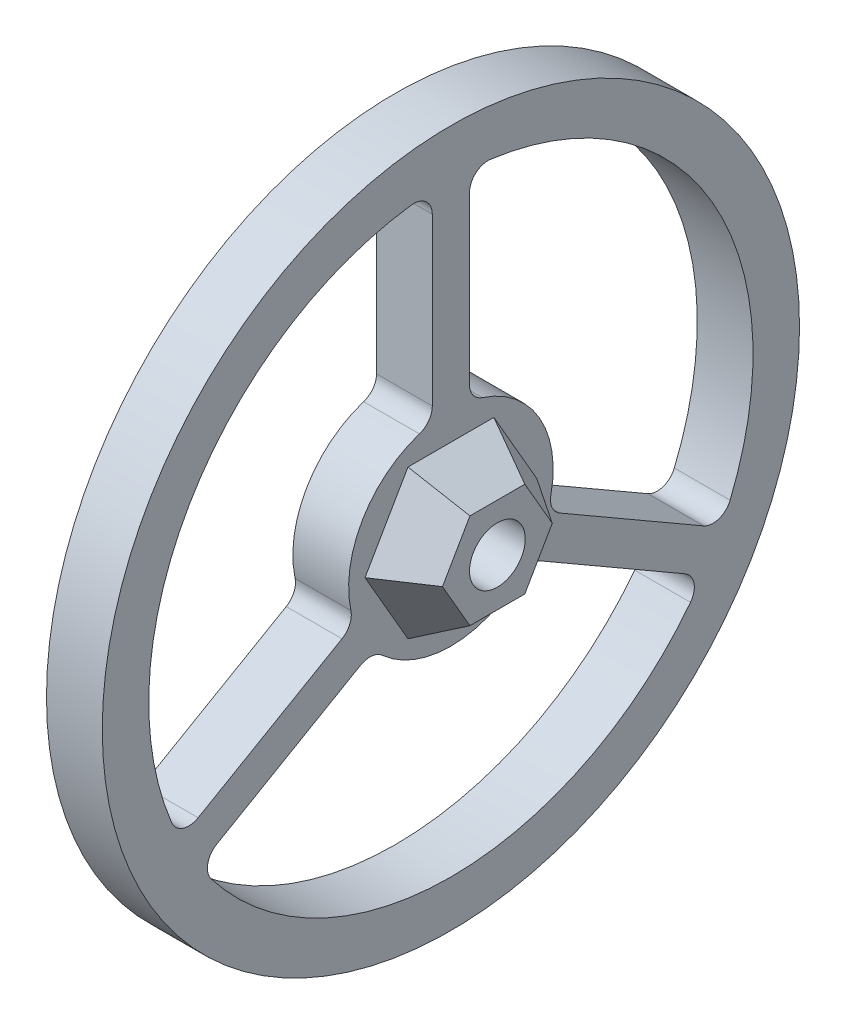
SolidWorks part; units mm, degrees
material "Acrylic (Medium-high impact)"
ref_plane "Front Plane" through (0, 0, 0) normal (0, 0, 1) x (1, 0, 0)
ref_plane "Top Plane" through (0, 0, 0) normal (0, 1, 0) x (1, 0, 0)
ref_plane "Right Plane" through (0, 0, 0) normal (1, 0, 0) x (0, 0, -1)
sketch "Sketch1" plane through (0, 0, 0) normal (1, 0, 0) x (0, 0, -1)
  line L0 (0, 0) -> (0, 37.5) construction
  line L1 (-2, 32.4384) -> (-2, 10.8167)
  line L2 (2, 32.4384) -> (2, 10.8167)
  line L3 (29.0925, -14.4872) -> (10.3675, -3.6763)
  line L4 (27.0925, -17.9513) -> (8.3675, -7.1404)
  line L5 (-27.0925, -17.9513) -> (-8.3675, -7.1404)
  line L6 (-29.0925, -14.4872) -> (-10.3675, -3.6763)
  circle A0 centre (0, 0) radius 37.5
  circle A2 centre (0, 0) radius 32.5
  circle A3 centre (0, 0) radius 3
  circle A4 centre (0, 0) radius 11
  point P23 (0, 0)
  dimension "D1" = 75
  dimension "D3" = 6
  dimension "D6" = 4
  dimension "D2" = 5
  dimension "D4" = 8
  dimension "D5" = 3
extrude "Boss-Extrude1" add sketch "Sketch1" along normal blind 6 contours A2 A0 | A3 A4 | A4 L6 A2 L5 | L0 A4 L2 A2 | A4 L0 A2 L1 | A4 L4 A2 L3 region at (0, 10.6442, -0.9758) region at (0, 21.7092, 1.0009) region at (0, 21.7092, -1.0009) region at (0, 25.7665, -25.7665) region at (0, -10.8546, 18.8007) region at (0, -10.8546, -18.8007)
fillet "Fillet1" radius 2 12 edges at (3, -3.6763, 10.3675) (3, -7.1404, 8.3675) (3, -7.1404, -8.3675) (3, -3.6763, -10.3675) (3, 10.8167, -2) (3, -17.9513, -27.0925) (3, -14.4872, -29.0925) (3, -17.9513, 27.0925) (3, -14.4872, 29.0925) (3, 32.4384, -2) (3, 32.4384, 2) (3, 10.8167, 2)
sketch "Sketch2" plane through (6, 0, 0) normal (1, 0, 0) x (0, 0, -1)
  line L1 (9.2376, 0) -> (4.6188, 8)
  line L2 (4.6188, 8) -> (-4.6188, 8)
  line L3 (-4.6188, 8) -> (-9.2376, 0)
  line L4 (-9.2376, 0) -> (-4.6188, -8)
  line L5 (-4.6188, -8) -> (4.6188, -8)
  line L6 (4.6188, -8) -> (9.2376, 0)
  circle A0 centre (0, 0) radius 8 construction
  dimension "D1" = 16
extrude "Boss-Extrude2" add sketch "Sketch2" along normal blind 5 draft 30
extrude "Cut-Extrude1" cut sketch "Sketch1<6>" along normal blind 20 contours A3 region at (0, 0, 0)
sketch "Sketch1<6>" plane through (0, 0, 0) normal (1, 0, 0) x (0, 0, -1) same geometry as "Sketch1"
